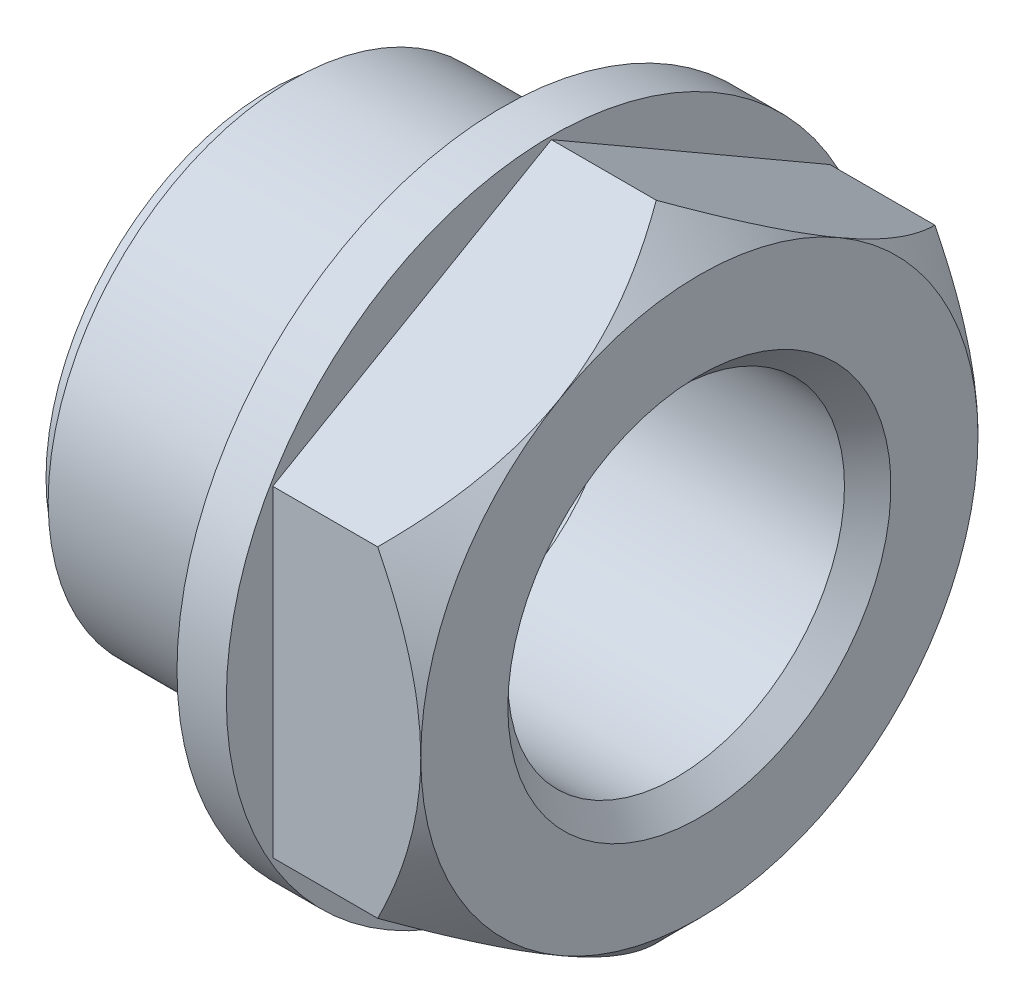
SolidWorks part; units mm, degrees
ref_plane "Piano frontale" through (0, 0, 0) normal (0, 0, 1) x (1, 0, 0)
ref_plane "Piano superiore" through (0, 0, 0) normal (0, 1, 0) x (1, 0, 0)
ref_plane "Piano destro" through (0, 0, 0) normal (1, 0, 0) x (0, 0, -1)
ref_plane "Piano1" through (0, 0, 0) normal (0, 0, 1) x (1, 0, 0)
sketch "Schizzo1" plane through (0, 0, 0) normal (0, 0, 1) x (1, 0, 0)
  line L0 (0, 8.25) -> (7.6923, 8.25)
  line L1 (7.6923, 8.25) -> (7.6923, 7.25)
  line L2 (7.6923, 7.25) -> (17.5, 7.25)
  line L3 (17.5, 7.25) -> (18.5, 8.25)
  line L4 (18.5, 8.25) -> (18.5, 12)
  line L5 (18.5, 12) -> (16.5, 14)
  line L6 (16.5, 14) -> (10, 14)
  line L7 (10, 14) -> (10, 10.48)
  line L8 (10, 10.48) -> (0.9316, 10.48)
  line L9 (0.9316, 10.48) -> (0.9316, 9.6416)
  line L10 (0.9316, 9.6416) -> (0, 9.6416)
  line L11 (0, 9.6416) -> (0, 8.25)
  line L12 (18.5, 0) -> (0, 0) construction
revolve "Rivoluzione1" add sketch "Schizzo1" angle 360 about L12 reverse direction yes
ref_plane "Piano2" through (18.5, 0, 0) normal (1, 0, 0) x (0, 0, -1)
sketch "Schizzo2" plane through (18.5, 0, 0) normal (1, 0, 0) x (0, 0, -1)
  line L0 (-18, -10.3923) -> (1, -21.362)
  line L1 (1, -21.362) -> (1, -14.4338)
  line L2 (1, -14.4338) -> (-12, -6.9282)
  line L3 (-12, -6.9282) -> (-12, 6.9282)
  line L4 (-12, 6.9282) -> (1, 14.4338)
  line L5 (1, 14.4338) -> (1, 21.362)
  line L6 (1, 21.362) -> (-18, 10.3923)
  line L7 (-18, 10.3923) -> (-18, -10.3923)
extrude "Taglio-Estrusione1" cut sketch "Schizzo2" against normal blind 6.375 and the other way blind 6.375
ref_plane "Piano3" through (18.5, 0, 0) normal (1, 0, 0) x (0, 0, -1)
sketch "Schizzo3" plane through (18.5, 0, 0) normal (1, 0, 0) x (0, 0, -1)
  line L0 (-1, -14.4338) -> (-1, -21.362)
  line L1 (-1, -21.362) -> (18, -10.3923)
  line L2 (18, -10.3923) -> (18, 10.3923)
  line L3 (18, 10.3923) -> (-1, 21.362)
  line L4 (-1, 21.362) -> (-1, 14.4338)
  line L5 (-1, 14.4338) -> (12, 6.9282)
  line L6 (12, 6.9282) -> (12, -6.9282)
  line L7 (12, -6.9282) -> (-1, -14.4338)
extrude "Taglio-Estrusione2" cut sketch "Schizzo3" against normal blind 6.375 and the other way blind 6.375
